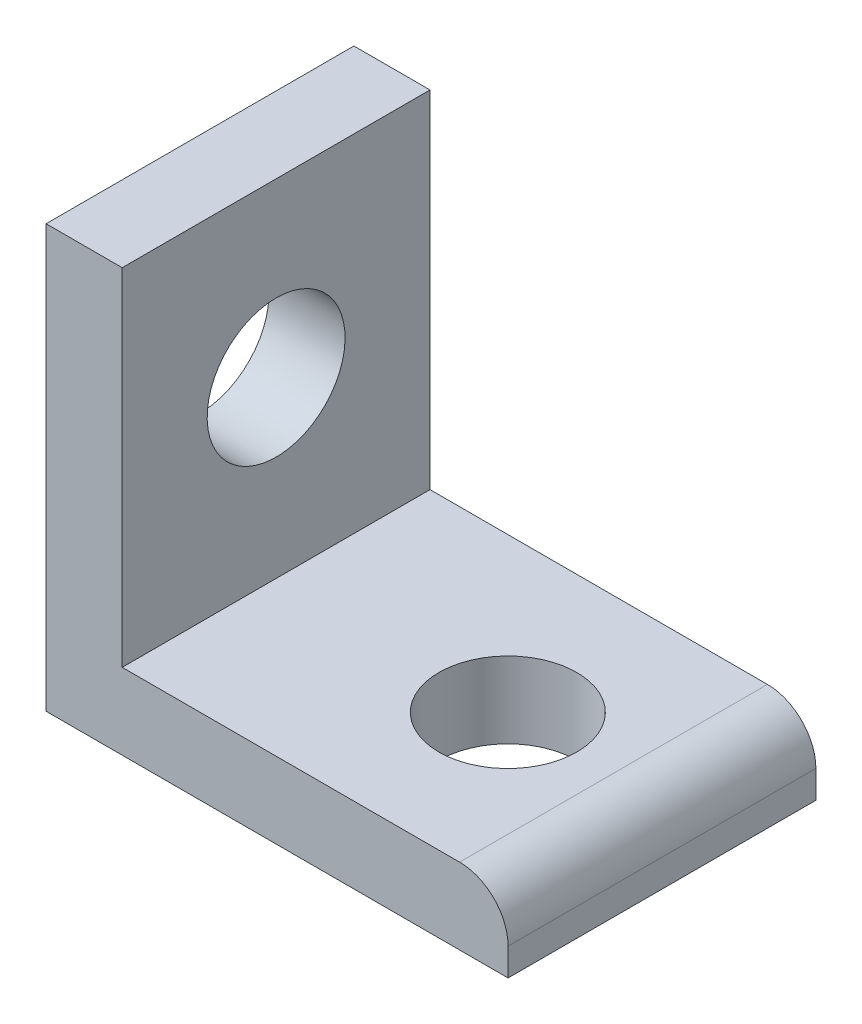
SolidWorks part; units mm, degrees
ref_plane "Front Plane" through (0, 0, 0) normal (0, 0, 1) x (1, 0, 0)
ref_plane "Top Plane" through (0, 0, 0) normal (0, 1, 0) x (1, 0, 0)
ref_plane "Right Plane" through (0, 0, 0) normal (1, 0, 0) x (0, 0, -1)
sketch "Sketch1" plane through (0, 0, 0) normal (0, 0, 1) x (1, 0, 0)
  line L0 (0, 8.71) -> (1.57, 8.71)
  line L1 (0, 0) -> (9.53, 0)
  line L2 (0, 0) -> (0, 8.71)
  line L3 (1.57, 8.71) -> (1.57, 1.57)
  line L4 (1.57, 1.57) -> (9.53, 1.57)
  line L5 (9.53, 1.57) -> (9.53, 0)
  dimension "D1" = 1.57
  dimension "D2" = 1.57
  dimension "D3" = 9.53
  dimension "D4" = 8.71
extrude "Boss-Extrude1" add sketch "Sketch1" along normal blind 6.35
sketch "Sketch2" plane through (0, 1.57, 0) normal (0, 1, 0) x (1, 0, 0)
  line L0 (9.53, -3.175) -> (-2.0199, -3.175) construction
  line L2 (9.53, -6.35) -> (9.53, 0) construction
  line L6 (0, -6.35) -> (0, 0) construction
  circle A0 centre (6.35, -3.175) radius 1.4225
  point P2 (0, -3.175)
  dimension "D1" = 2.845
  dimension "D2" = 6.35
extrude "Cut-Extrude1" cut sketch "Sketch2" against normal up to surface (1.57 mm away) up to face at (4.765, 0, 3.175)
sketch "Sketch3" plane through (1.57, 0, 0) normal (1, 0, 0) x (0, 0, -1)
  line L0 (-3.175, 8.71) -> (-3.175, -0.5665) construction
  line L1 (-6.35, 8.71) -> (0, 8.71) construction
  line L2 (-6.35, 0) -> (0, 0) construction
  circle A0 centre (-3.175, 5.16) radius 1.4225
  dimension "D1" = 2.845
  dimension "D2" = 5.16
extrude "Cut-Extrude2" cut sketch "Sketch3" against normal up to surface (1.57 mm away) up to face at (0, 4.355, 3.175)
fillet "Fillet1" radius 1 1 edges at (9.53, 1.57, 3.175)
